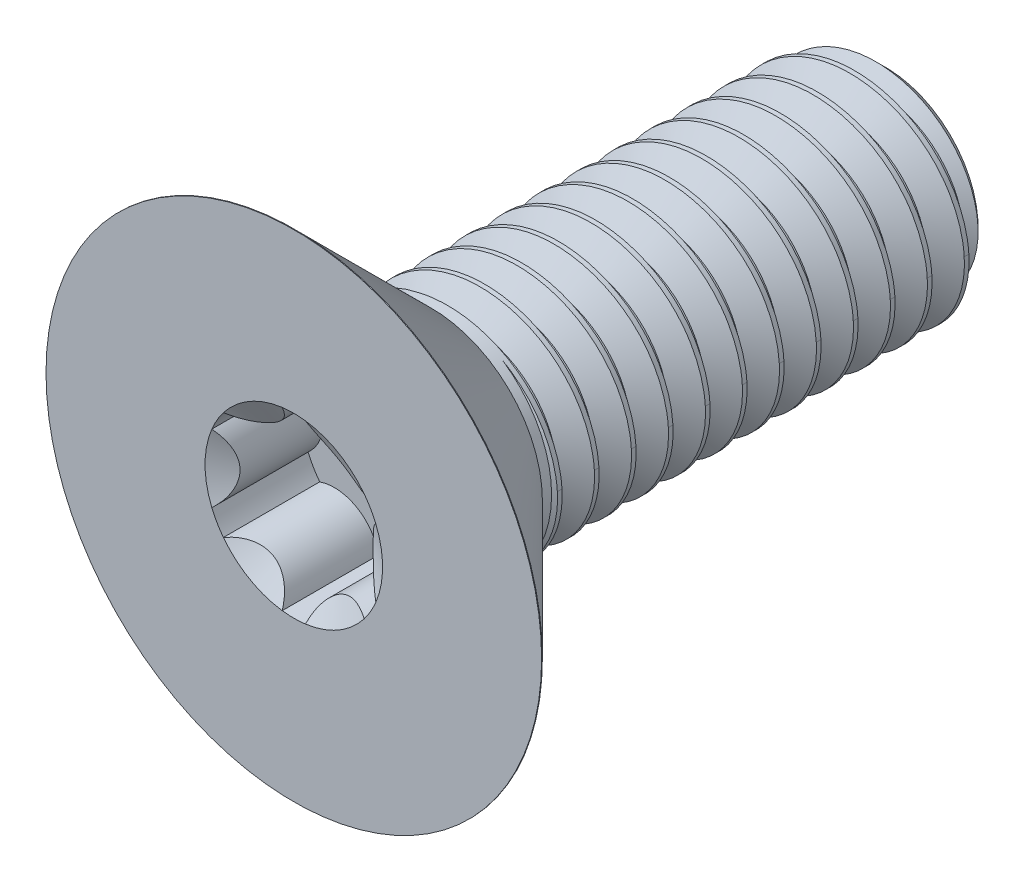
SolidWorks part; units mm, degrees
note: '?' marks a value the reader was unsure of.
ref_plane "Front" through (0, 0, 0) normal (0, 0, 1) x (1, 0, 0)
ref_plane "Top" through (0, 0, 0) normal (0, 1, 0) x (1, 0, 0)
ref_plane "Right" through (0, 0, 0) normal (1, 0, 0) x (0, 0, -1)
sketch "Sketch1" plane through (0, 0, 0) normal (1, 0, 0) x (0, 0, -1)
  line L0 (0, 3.35) -> (1.86, 3.35) construction
  line L2 (0, 0) -> (8, 0) construction
  line L4 (8, 1.5) -> (1.86, 1.5) construction
  line L5 (0, 0) -> (0, 3.35) construction
  line L6 (0, 3.35) -> (0, -3.35) construction
  line L7 (8, 1.5) -> (8, -1.5) construction
  line L8 (0, -3.35) -> (1.86, -3.35) construction
  line L9 (0.01, 3.35) -> (3.36, 0) construction
  line L11 (8, -1.5) -> (1.86, -1.5) construction
  line L13 (0.01, 3.35) -> (0.01, -3.35) construction
  line L14 (0.01, -3.35) -> (3.36, 0) construction
  line L15 (1.86, 3.35) -> (1.86, 1.5) construction
  line L16 (8, 1.5) -> (8.5, 1.5) construction
  point P5 (0.01, 3.35)
  point P17 (6.75, -1.5)
  dimension "Head Angle" = 90
  dimension "D1" = 1.25
sketch "Sketch12" plane through (0, 0, 0) normal (1, 0, 0) x (0, 0, -1)
  line L0 (0, 0) -> (8, 0)
  line L1 (8, 0) -> (8, 1.5)
  line L2 (8, 1.5) -> (1.86, 1.5)
  line L3 (1.86, 1.5) -> (0.01, 3.35)
  line L4 (0.01, 3.35) -> (0, 3.35)
  line L5 (0, 3.35) -> (0, 0)
revolve "Revolve3" add sketch "Sketch12" angle 360 about L0
chamfer "Chamfer1" distance 0.25 angle 45 1 edges at (1.5, 0, -8)
sketch "Sketch5" plane through (0, 0, 0) normal (0, 0, 1) x (1, 0, 0)
  line L0 (0, 0) -> (-1.2, 0) construction
  line L1 (0, 0) -> (-1.0392, 0.6) construction
  line L2 (0, 0) -> (-1.0392, -0.6) construction
  line L3 (-1.0392, -0.6) -> (0, 0)
  line L4 (0, 0) -> (-1.0392, 0.6)
  line L5 (0, 0) -> (-1.1087, -0.4592) construction
  line L6 (0, 1.2) -> (0, 1.05) construction
  line L7 (0, 1.05) -> (0, 0.9) construction
  circle A0 centre (0, 0) radius 1.2 construction
  circle A1 centre (0, 0) radius 1.05 construction
  circle A2 centre (0, 0) radius 0.9 construction
  arc A4 (-1.1087, -0.4592) -> (-1.1087, 0.4592) centre (-1.5097, 0) ccw
  arc A5 (-1.1087, 0.4592) -> (-1.0392, 0.6) centre (0, 0) cw
  arc A6 (-1.1087, -0.4592) -> (-1.0392, -0.6) centre (0, 0) ccw
  point P13 (0, -0.9)
  dimension "D3" = 1.8
  dimension "D4" = 30
  dimension "D5" = 30
  dimension "D1" = 7.5
extrude "Cut-Extrude2" cut sketch "Sketch5" against normal blind 1.302
pattern_circular "CirPattern1" count 6 over 360 about axis through (0, 0, 0) along (0, 0, 1) of "Cut-Extrude2"
sketch "Sketch6" plane through (0, 0, 0) normal (0, 0, 1) x (1, 0, 0)
  circle A0 centre (0, 0) radius 1.2
extrude "Cut-Extrude3" cut sketch "Sketch6" against normal blind 1.302 draft 60
ref_plane "Plane1" through (0, 0, -1.86) normal (0, 0, 1) x (1, 0, 0)
split "Split1" trim tools "Plane1" bodies to split 113 resulting bodies 132 133
sketch "Sketch13" plane through (0, 0, -8) normal (0, 0, -1) x (-1, 0, 0)
  circle A0 centre (0, 0) radius 1.5
curve "Helix/Spiral1" pitch 0.5 height 6.754 turns 13.508
sketch "Sketch14" plane through (0, 0, 0) normal (1, 0, 0) x (0, 0, -1)
  line L0 (7.9688, 1.5541) -> (8.4688, 1.5541) construction
  line L1 (8.4688, 1.5541) -> (8.2188, 1.1211) construction
  line L2 (8.2188, 1.1211) -> (7.9688, 1.5541) construction
  line L3 (8.2188, 1.1211) -> (8.2188, 1.1752) construction
  line L4 (8.2188, 1.1752) -> (8.2188, 1.5) construction
  line L5 (8.2188, 1.5) -> (8.2188, 1.5541) construction
  line L6 (8, 1.5) -> (8.4375, 1.5) construction
  line L8 (7.9844, 1.5271) -> (8.4531, 1.5271) construction
  line L9 (8.1875, 1.1752) -> (8.25, 1.1752)
  line L10 (8.1875, 1.1752) -> (8.25, 1.1752) construction
  line L11 (8.25, 1.1752) -> (8.4531, 1.5271)
  line L12 (8.4531, 1.5271) -> (7.9844, 1.5271)
  line L13 (7.9844, 1.5271) -> (8.1875, 1.1752)
  point P8 (8.2188, 1.5)
  point P13 (8.2188, 1.1752)
  point P15 (8.2188, 1.5271)
  point P16 (8.2188, 1.5271)
  dimension "D1" = 0.5
  dimension "D2" = 0.0625
sweep "Cut-Sweep2" cut profiles "Sketch14" path "Helix/Spiral1" align with end faces yes
sketch "Sketch15" plane through (0, 0, 0) normal (1, 0, 0) x (0, 0, -1)
  line L0 (1.86, 1.5) -> (1.985, 1.5)
  line L1 (8, 1.5) -> (1.86, 1.5) construction
  line L2 (1.985, 1.5) -> (2.851, 0)
  line L3 (0, 0) -> (8, 0) construction
  line L6 (1.86, 1.5) -> (1.86, 0)
  line L7 (1.86, -1.5) -> (1.86, 1.5) construction
  line L8 (1.86, 0) -> (2.851, 0)
  dimension "D2" = 0.125
  dimension "D1" = 60
revolve "Revolve4" add sketch "Sketch15" angle 360 about L2
ref_axis "Center Axis 1" through (0, 0, -0.8702) along (0, 0, -1)?
ref_plane "Contact Plane 1" through (0, 0, -8) normal (0, 0, -1) x (-1, 0, 0)
ref_plane "Contact Plane 2" through (0, 0, 0) normal (0, 0, 1) x (1, 0, 0)
equation "\"D1@Cut-Extrude2\" = \"Head Ht@Sketch1\" * .7"
equation "\"D1@Cut-Extrude3\" = \"D1@Cut-Extrude2\""
equation "\"Torx Dia@Sketch5\" = \"Dia@Sketch1\" * .8"
equation "\"D3@Sketch5\" = \"Torx Dia@Sketch5\" * .75"
equation "\"D1@Chamfer1\"=\"Pitch@Sketch1\"*.5"
equation "\"D3@Helix/Spiral1\"=(\"Lg@Sketch1\"-\"Head Ht@Sketch1\")*1.1"
equation "\"D4@Helix/Spiral1\"=\"Pitch@Sketch1\""
equation "\"D1@Sketch14\"=\"pITCH@sKETCH1\""
equation "\"D2@Sketch14\"=\"D1@Sketch14\"/8"
equation "\"D2@Sketch15\"=\"Pitch@Sketch1\"*.25"
equation "\"D1@Sketch1\"=\"Pitch@Sketch1\"*2.5"
